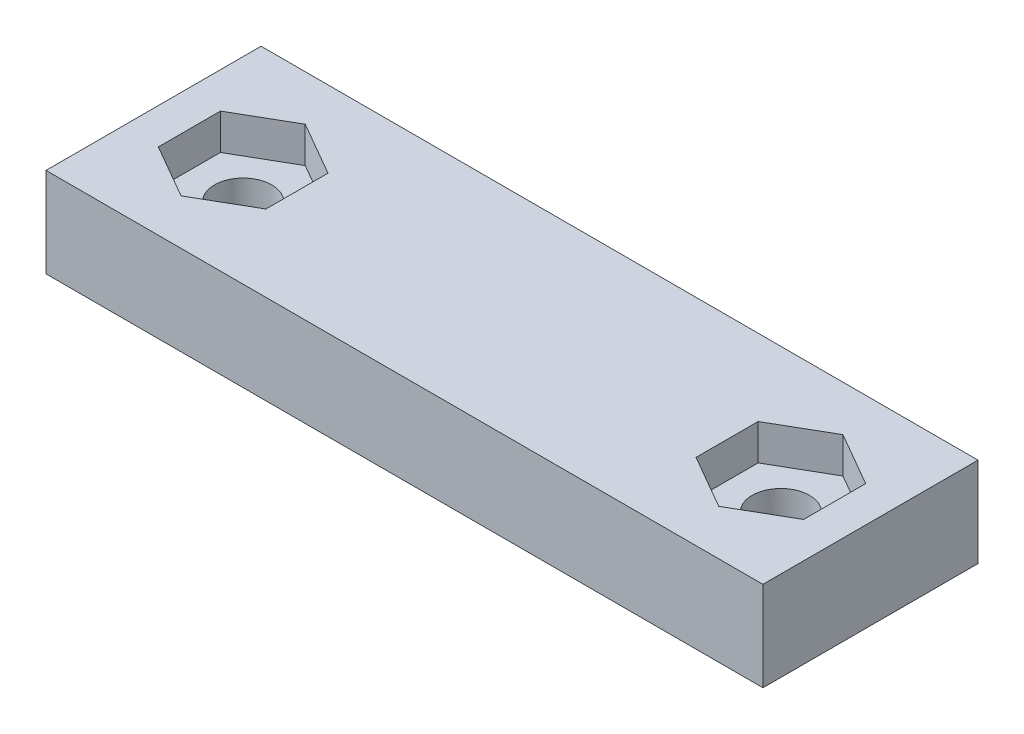
SolidWorks part; units mm, degrees
ref_plane "Front Plane" through (0, 0, 0) normal (0, 0, 1) x (1, 0, 0)
ref_plane "Top Plane" through (0, 0, 0) normal (0, 1, 0) x (1, 0, 0)
ref_plane "Right Plane" through (0, 0, 0) normal (1, 0, 0) x (0, 0, -1)
sketch "Sketch1" plane through (0, 0, 0) normal (0, 1, 0) x (1, 0, 0)
  line L1 (-20, 6) -> (20, 6)
  line L2 (-20, 6) -> (-20, -6)
  line L3 (-20, -6) -> (20, -6)
  line L4 (20, 6) -> (20, -6)
  line L5 (-20, 6) -> (20, -6) construction
  line L6 (-20, -6) -> (20, 6) construction
  point P0 (0, 0)
  dimension "D1" = 40
  dimension "D2" = 12
extrude "Boss-Extrude1" add sketch "Sketch1" along normal blind 5
sketch "Sketch2" plane through (0, 5, 0) normal (0, 1, 0) x (1, 0, 0)
  line L0 (-20, 0) -> (20, 0) construction
  line L1 (-20, 6) -> (-20, -6) construction
  line L2 (20, -6) -> (20, 6) construction
  line L3 (0, -6) -> (0, 7.5) construction
  line L4 (-20, -6) -> (20, -6) construction
  line L5 (20, 6) -> (-20, 6) construction
  circle A0 centre (15, 0) radius 1.6
  circle A1 centre (-15, 0) radius 1.6
  point P17 (0, 6)
  dimension "D1" = 3.2
  dimension "D2" = 15
extrude "Cut-Extrude2" cut sketch "Sketch2" against normal through all
sketch "Sketch3" plane through (-20, 0, 0) normal (-1, 0, 0) x (0, 0, 1)
  line L0 (-5.25, 1) -> (-5.25, 0)
  line L2 (-5.25, 0) -> (-4.25, 0)
  line L3 (-4.25, 0) -> (-4.25, 1)
  line L4 (-4.25, 1) -> (-5.25, 1)
  line L5 (-3.25, 0) -> (-2.25, 0)
  line L6 (-3.25, 1) -> (-3.25, 0)
  line L7 (-2.25, 0) -> (-2.25, 1)
  line L8 (-2.25, 1) -> (-3.25, 1)
  line L9 (-1.25, 0) -> (-0.25, 0)
  line L10 (-1.25, 1) -> (-1.25, 0)
  line L11 (-0.25, 0) -> (-0.25, 1)
  line L12 (-0.25, 1) -> (-1.25, 1)
  line L13 (0.75, 0) -> (1.75, 0)
  line L14 (0.75, 1) -> (0.75, 0)
  line L15 (1.75, 0) -> (1.75, 1)
  line L16 (1.75, 1) -> (0.75, 1)
  line L17 (2.75, 0) -> (3.75, 0)
  line L18 (2.75, 1) -> (2.75, 0)
  line L19 (3.75, 0) -> (3.75, 1)
  line L20 (3.75, 1) -> (2.75, 1)
  line L21 (4.75, 0) -> (5.75, 0)
  line L22 (4.75, 1) -> (4.75, 0)
  line L23 (5.75, 0) -> (5.75, 1)
  line L24 (5.75, 1) -> (4.75, 1)
  line L25 (6.75, 0) -> (7.75, 0)
  line L26 (6.75, 1) -> (6.75, 0)
  line L27 (7.75, 0) -> (7.75, 1)
  line L28 (7.75, 1) -> (6.75, 1)
  line L29 (8.75, 0) -> (9.75, 0)
  line L30 (8.75, 1) -> (8.75, 0)
  line L31 (9.75, 0) -> (9.75, 1)
  line L32 (9.75, 1) -> (8.75, 1)
  line L33 (-6, 5) -> (-6, 0) construction
  line L34 (-6, 0) -> (6, 0) construction
  dimension "D1" = 1
  dimension "D3" = 0.75
  dimension "D4" = 1
  dimension "D5" = 1
  dimension "D6" = 0
  dimension "D7" = 1
  dimension "D2" = 8
extrude "Teeth" cut sketch "Sketch3" against normal blind 5 and the other way blind 5 from surface starting at plane "Right Plane"
sketch "Sketch4" plane through (0, 5, 0) normal (0, 1, 0) x (1, 0, 0)
  line L0 (-15, 0) -> (-15, 3.4641) construction
  line L1 (-15, 3.4641) -> (-18, 1.7321)
  line L2 (-18, 1.7321) -> (-18, -1.7321)
  line L3 (-18, -1.7321) -> (-15, -3.4641)
  line L4 (-15, -3.4641) -> (-12, -1.7321)
  line L5 (-12, -1.7321) -> (-12, 1.7321)
  line L6 (-12, 1.7321) -> (-15, 3.4641)
  line L7 (0, 6) -> (0, -7.5) construction
  line L8 (20, 6) -> (-20, 6) construction
  line L10 (15, 0) -> (15, 3.4641) construction
  line L11 (12, 1.7321) -> (15, 3.4641)
  line L12 (12, -1.7321) -> (12, 1.7321)
  line L13 (15, -3.4641) -> (12, -1.7321)
  line L14 (18, -1.7321) -> (15, -3.4641)
  line L15 (18, 1.7321) -> (18, -1.7321)
  line L16 (15, 3.4641) -> (18, 1.7321)
  line L17 (-15, 0) -> (-15, 3.4641) construction
  circle A0 centre (-15, 0) radius 3 construction
  circle A1 centre (15, 0) radius 3 construction
  dimension "D1" = 6
extrude "Cut-Extrude4" cut sketch "Sketch4" against normal blind 2
equation "\"X-ROD-SPACING\"=45"
equation "\"Y-ROD-SPACING\"=75"
equation "\"Z-ROD-SPACING\"=17.5"
equation "\"Y-BED-OFFSET\"=2"
equation "\"Y-BED-ROD-INSET\"=3.5"
equation "\"T-SLOT-NUT-FILLET-RADIUS\"=0.25"
equation "\"T-SLOT-SCREW-SHAFT-RADIUS\"=1.75"
equation "\"T-SLOT-SCREW-SHAFT-CUTOUT-LENGTH\"=10.5"
equation "\"T-SLOT-NUT-DEPTH\"=4.2"
equation "\"T-SLOT-NUT-WIDTH\"=3"
equation "\"T-SLOT-NUT-END-DISTANCE\"=8"
equation "\"ACRYLIC-THICKNESS\"=10"
equation "\"ACRYLIC-THICKNESS2\"=4.5"
equation "\"ACRYLIC-TAB-CUTOUT-SIZE\"=\"ACRYLIC-THICKNESS\"+\"ACRYLIC-TAB-TOLERANCE\"*2"
equation "\"ACRYLIC-TAB-WIDTH\"=\"ACRYLIC-THICKNESS\""
equation "\"ACRYLIC-M3-HOLE\"=3.1"
equation "\"SMOOTHROD-CAP-SCREW-DISTANCE\"=20"
equation "\"FRAME-WIDTH-INNER\"=370"
equation "\"NEMA17-HOLE-SPACING\"=31"
equation "\"NEMA17-CENTRAL-CUTOUT\"=22.5"
equation "\"Z-BRACKET-REACH\"=55"
equation "\"TOP-BRACKET-SPACING\"=40"
equation "\"SMOOTHROD-X-LENGTH\"=350"
equation "\"SMOOTHROD-Y-LENGTH\"=350"
equation "\"SMOOTHROD-Z-LENGTH\"=350"
equation "\"SMOOTHROD-TIGHTENING-HEADROOM\"=1"
equation "\"LEADSCREW-Z-LENGTH\"=300"
equation "\"SCREW-LENGTH-FRAME\"=\"ACRYLIC-THICKNESS\" + 10"
equation "\"SCREW-HEAD-RADIUS\"=6"
equation "\"PRINTED-X-SMOOTHROD-DIAMETER\"=8.2"
equation "\"PRINTED-X-SMOOTHROD-CUTOUT\"=10"
equation "\"PRINTED-X-BASE-HEIGHT\"=10"
equation "\"PRINTED-LM8UU-CUTOUT-SIZE\"=15.25"
equation "\"PRINTED-LM8UU-CUTOUT-LENGTH\"=24.5"
equation "\"PRINTED-X-IDLER-HEIGHT\"=16"
equation "\"PSU-MOUNTING-WIDTH\"=95"
equation "\"PSU-MOUNTING-HEIGHT\"=177"
equation "\"Y-BELT-TO-ROD-DISTANCE\"=20"
equation "\"D1@Sketch4\"=\"T-SLOT-NUT-WIDTH\"*2"
